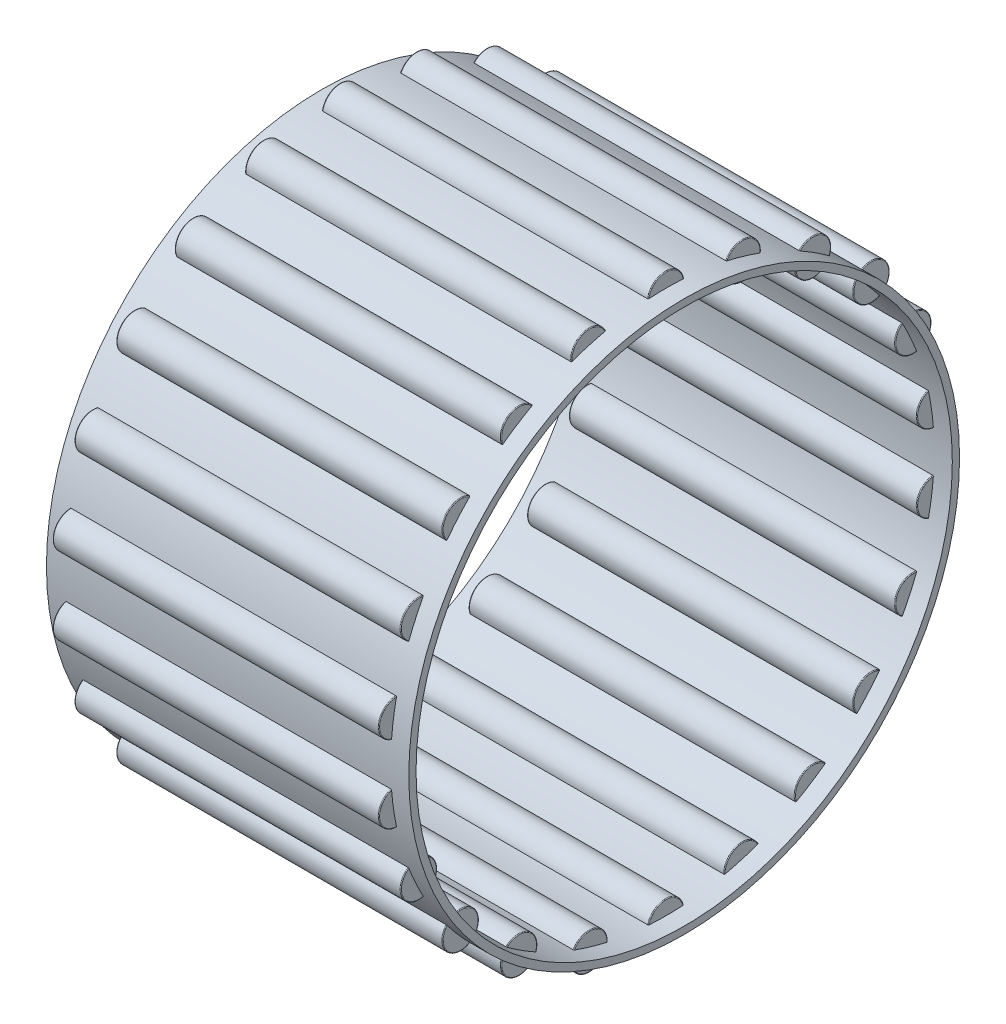
SolidWorks part; units mm, degrees
ref_plane "Plane1" through (0, 0, 0) normal (0, 0, 1) x (1, 0, 0)
ref_plane "Plane2" through (0, 0, 0) normal (0, 1, 0) x (1, 0, 0)
ref_plane "Plane3" through (0, 0, 0) normal (1, 0, 0) x (0, 0, -1)
sketch "Clipboard" plane through (0, 0, 0) normal (0, 0, 1) x (1, 0, 0)
  line L0 (-10, 0) -> (10, 0) construction
  line L1 (0, 0) -> (20.7325, -8.3765)
  line L2 (0, 0) -> (47.1009, 19.03)
  line L3 (0, 0) -> (23.8125, -9.6209)
  line L4 (0, 0) -> (-44.45, -1.5522)
  dimension "Bore" = 44.45
sketch "CagSpiSke" plane through (0, 0, 0) normal (0, 0, 1) x (1, 0, 0)
  line L0 (15.875, 23.495) -> (15.875, 24.13)
  line L1 (15.875, 24.13) -> (-15.875, 24.13)
  line L2 (-15.875, 24.13) -> (-15.875, 23.495)
  line L3 (-15.875, 23.495) -> (15.875, 23.495)
  line L4 (-12.7, 0) -> (12.7, 0) construction
revolve "CageSpine" add sketch "CagSpiSke" angle 360 about L4 reverse direction yes
sketch "RolDetSke" plane through (0, 0, 0) normal (0, 0, 1) x (1, 0, 0)
  line L0 (-17.78, 23.8125) -> (17.78, 23.8125) construction
  line L2 (-14.224, 25.4) -> (14.224, 25.4)
  line L3 (-14.2875, 25.3365) -> (-14.2875, 23.8125)
  line L5 (-14.2875, 23.8125) -> (14.2875, 23.8125)
  line L6 (14.2875, 25.3365) -> (14.2875, 23.8125)
  arc A0 (-14.224, 25.4) -> (-14.2875, 25.3365) centre (-14.224, 25.3365) ccw
  arc A1 (14.2875, 25.3365) -> (14.224, 25.4) centre (14.224, 25.3365) ccw
  dimension "radius" = 0.0635
  dimension "CLRad" = 23.8125
  dimension "Cyl_Len" = 28.575
  dimension "Roller_diameter" = 3.175
revolve "RollerDetailed" add sketch "RolDetSke" angle 360 about L0 reverse direction yes
ref_axis "Axis1" through (-50, 0, 0) along (1, 0, 0)
pattern_circular "RollersDetailed" count 22 every 16.364 about axis through (-50, 0, 0) along (1, 0, 0) of "RollerDetailed"
sketch "RolSimSke" plane through (0, 0, 0) normal (0, 0, 1) x (1, 0, 0)
  line L0 (-17.78, 0) -> (17.78, 0) construction
  line L1 (-12.7, 0) -> (-38.1, 0) construction
  line L3 (-14.224, 25.4) -> (14.224, 25.4)
  line L4 (-14.2875, 25.3365) -> (-14.2875, 22.2885)
  line L5 (-14.224, 22.225) -> (14.224, 22.225)
  line L6 (14.2875, 25.3365) -> (14.2875, 22.2885)
  arc A0 (14.2875, 22.2885) -> (14.224, 22.225) centre (14.224, 22.2885) cw
  arc A1 (14.224, 25.4) -> (14.2875, 25.3365) centre (14.224, 25.3365) cw
  arc A2 (-14.2875, 25.3365) -> (-14.224, 25.4) centre (-14.224, 25.3365) cw
  arc A3 (-14.224, 22.225) -> (-14.2875, 22.2885) centre (-14.224, 22.2885) cw
  point P13 (14.2875, 25.4)
  point P16 (-14.2875, 25.4)
  point P19 (-14.2875, 22.225)
  dimension "radius" = 0.0635
  dimension "Cyl_Len" = 28.575
  dimension "Roller_diameter" = 3.175
  dimension "Bore" = 44.45
  dimension "D1" = 14.2875
revolve "RollersSimplified" [suppressed] add sketch "RolSimSke" angle 360 about L0
equation "\"RollCLRad@Clipboard\" = ( \"OD@Clipboard\" + \"Bore@Clipboard\" )  / 4"
equation "\"CLRad@RolDetSke\" = \"RollCLRad@Clipboard\""
equation "\"thickness@CagSpiSke\"  = ( \"OD@Clipboard\" - \"Bore@Clipboard\" )  / 10"
equation "\"cagRadius@CagSpiSke\" =  \"RollCLRad@Clipboard\" -  ( \"thickness@CagSpiSke\" / 2 ) "
equation "\"halfWidth@CagSpiSke\" = \"Width@CagSpiSke\" / 2"
equation "\"Bore@RolSimSke\" = \"Bore@Clipboard\""
equation "\"Roller_diameter@RolDetSke\" =  ( \"OD@Clipboard\" - \"Bore@Clipboard\" )  / 2"
equation "\"halfCylLen@RolDetSke\" = \"Cyl_Len@RolDetSke\" / 2"
equation "\"radius@RolDetSke\" = \"Roller_diameter@RolDetSke\" / 50"
equation "\"Cyl_Len@RolSimSke\" = \"Cyl_Len@RolDetSke\""
equation "\"D1@RolSimSke\" = \"Cyl_Len@RolSimSke\"/2"
equation "\"radius@RolSimSke\" = \"radius@RolDetSke\""
equation "\"Roller_diameter@RolSimSke\" =  ( \"OD@Clipboard\" - \"Bore@Clipboard\" )  / 2"
equation "\"Max_count@Clipboard\" = int( 3.14159265 / atn(( \"Roller_diameter@RolDetSke\" / 2) / sqr(\"RollCLRad@Clipboard\"  * \"RollCLRad@Clipboard\" - ( \"Roller_diameter@RolDetSke\" / 2) *  ( \"Roller_diameter@RolDetSke\" / 2))))"
equation "\"Max_count@Clipboard\" = ((sgn( \"Max_count@Clipboard\" - \"Count@Clipboard\" )-1)*( \"Max_count@Clipboard\" - \"Count@Clipboard\" ))/-2+ \"Count@Clipboard\""
equation "\"Count@RollersDetailed\" = int( \"Show_count@Clipboard\" ) "
equation "\"Count@RollersDetailed\" = ((sgn( \"Count@RollersDetailed\" - \"Max_count@Clipboard\" )-1)*( \"Count@RollersDetailed\" - \"Max_count@Clipboard\" ))/-2+ \"Max_count@Clipboard\""
equation "\"Count@RollersDetailed\" = ((sgn( \"Count@RollersDetailed\" - \"Min_count@Clipboard\" )+1)*( \"Count@RollersDetailed\" - \"Min_count@Clipboard\"))/2 +\"Min_count@Clipboard\""
equation "\"Angle@RollersDetailed\" = 360.0 / \"Max_count@Clipboard\""
